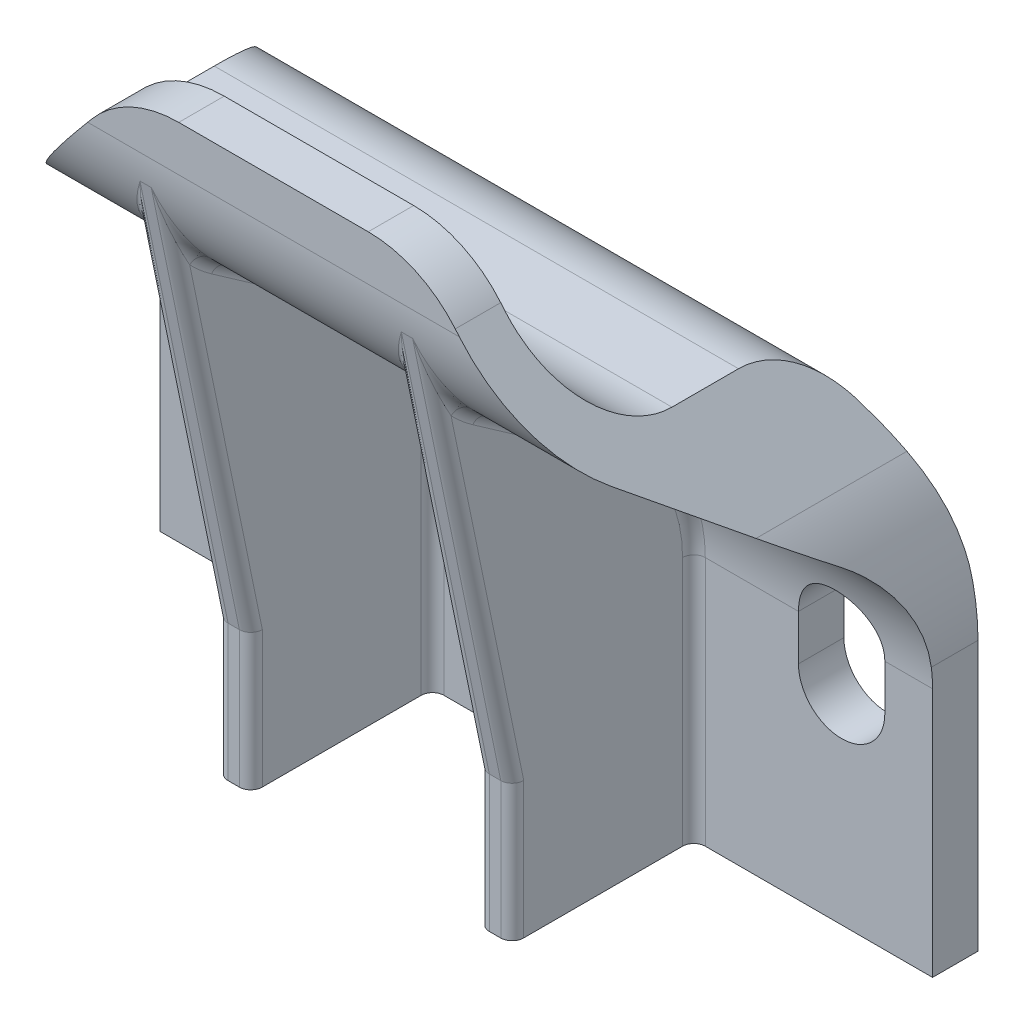
SolidWorks part; units mm, degrees
material "acero"
ref_plane "Alzado" through (0, 0, 0) normal (0, 0, 1) x (1, 0, 0)
ref_plane "Planta" through (0, 0, 0) normal (0, 1, 0) x (1, 0, 0)
ref_plane "Vista lateral" through (0, 0, 0) normal (1, 0, 0) x (0, 0, -1)
sketch "Croquis1" plane through (0, 0, 0) normal (1, 0, 0) x (0, 0, -1)
  line L0 (0, 0) -> (0, 8)
  line L1 (-5.0718, 16) -> (-8, 16)
  line L2 (-12, 20) -> (-12, 22)
  line L3 (-2, 0) -> (-2, 5)
  line L4 (-12, 22) -> (-14, 22)
  line L5 (-2, 0) -> (0, 0)
  line L6 (-14, 22) -> (-14, 20)
  line L7 (-11.4415, 15.0851) -> (-4.8458, 10.4668)
  arc A0 (-1.6077, 14) -> (-5.0718, 16) centre (-5.0718, 12) ccw
  arc A1 (-14, 20) -> (-11.4415, 15.0851) centre (-8, 20) ccw
  arc A2 (-8, 16) -> (-12, 20) centre (-8, 20) cw
  arc A3 (0, 8) -> (-1.6077, 14) centre (-12, 8) ccw
  arc A4 (-4.8458, 10.4668) -> (-2, 5) centre (-8.6737, 5) cw
  dimension "D5" = 12
  dimension "D7" = 2
  dimension "D13" = 22
  dimension "D14" = 12
  dimension "D3" = 35
  dimension "D6" = 16
  dimension "D8" = 4
  dimension "D2" = 8
  dimension "D4" = 2
  dimension "D10" = 5
extrude "Saliente-Extruir1" add sketch "Croquis1" along normal blind 34
sketch "Croquis2" plane through (0, 0, 2) normal (0, 0, 1) x (1, 0, 0)
  line L0 (17, 5) -> (17, 0) construction
  line L1 (4, 5) -> (4, 3) construction
  line L2 (5.9, 5) -> (5.9, 3)
  line L3 (34, 0) -> (0, 0) construction
  line L4 (2.1, 5) -> (2.1, 3)
  line L5 (34, 5) -> (0, 5) construction
  line L6 (30, 5) -> (30, 3) construction
  line L7 (28.1, 5) -> (28.1, 3)
  line L8 (31.9, 5) -> (31.9, 3)
  circle A0 centre (4, 3) radius 1.9 construction
  circle A1 centre (30, 3) radius 1.9 construction
  circle A2 centre (4, 3) radius 1.5 construction
  circle A3 centre (30, 3) radius 1.5 construction
  circle A4 centre (4, 3) radius 3.25 construction
  arc A5 (5.9, 5) -> (2.1, 5) centre (4, 5) ccw
  arc A6 (2.1, 3) -> (5.9, 3) centre (4, 3) ccw
  arc A7 (28.1, 5) -> (31.9, 5) centre (30, 5) cw
  arc A8 (31.9, 3) -> (28.1, 3) centre (30, 3) cw
  point P7 (4, 4)
  point P20 (30, 4)
  dimension "D1" = 26
  dimension "D2" = 6.5
  dimension "D3" = 3
  dimension "D4" = 3.8
  dimension "D5" = 3
  dimension "D6" = 2
extrude "Cortar-Extruir1" cut sketch "Croquis2" against normal through all both and the other way through all
chamfer "Chaflán2" [suppressed] distance 0.4 angle 60
ref_plane "Plano1" through (17, 0, 0) normal (-1, 0, 0) x (0, 0, 1)
sketch "Croquis3" plane through (17, 0, 0) normal (-1, 0, 0) x (0, 0, 1)
  line L0 (2, 0) -> (10, 0)
  line L1 (10, 0) -> (13.8762, 18.7876)
  line L2 (2, 0) -> (2, 5)
  line L3 (4.8458, 10.4668) -> (11.4415, 15.0851)
  arc A0 (11.4415, 15.0851) -> (14, 20) centre (8, 20) ccw construction
  arc A1 (2, 5) -> (4.8458, 10.4668) centre (8.6737, 5) cw
  arc A2 (11.4415, 15.0851) -> (13.8762, 18.7876) centre (8, 20) ccw
  dimension "D1" = 8
extrude "Saliente-Extruir2" add sketch "Croquis3" along normal blind 1.5 from offset 5
extrude "Saliente-Extruir3" add sketch "Croquis3<2>" against normal blind 1.5 from offset 5 offset against normal yes
sketch "Croquis3<2>" plane through (17, 0, 0) normal (-1, 0, 0) x (0, 0, 1) same geometry as "Croquis3"
sketch "Croquis4" plane through (0, 0, 0) normal (0, 0, -1) x (-1, 0, 0)
  line L0 (-10.5, 18.7876) -> (-10.5, 22) construction
  line L1 (-34, 22) -> (0, 22) construction
  line L2 (-17, 0) -> (-17, 22) construction
  line L3 (-22, 0) -> (-12, 0) construction
  line L4 (-34, 22) -> (-34, 9.4866)
  line L5 (0, 9.4866) -> (-10.5, 22)
  line L6 (-10.5, 22) -> (0, 22)
  line L7 (0, 22) -> (0, 9.4866)
  line L8 (-23.5, 22) -> (-34, 22)
  line L9 (-34, 9.4866) -> (-23.5, 22)
  dimension "D1" = 50
extrude "Cortar-Extruir2" cut sketch "Croquis4" against normal through all
fillet "Redondeo7" radius 5 2 edges at (23.5, 22, 13) (10.5, 22, 13)
fillet "Redondeo8" radius 10 2 edges at (34, 9.4866, 1.9128) (0, 9.4866, 1.9128)
fillet "Redondeo9" radius 0.5 20 edges at (22, 16.7033, 13.0132) (22, 12.7759, 8.1436) (22, 2.5, 2) (23.5, 16.7033, 13.0132) (23.5, 12.7759, 8.1436) (23.5, 2.5, 2) (12, 16.7033, 13.0132) (12, 12.7759, 8.1436) (12, 2.5, 2) (10.5, 16.7033, 13.0132) (10.5, 12.7759, 8.1436) (10.5, 8.0816, 2.7541) (22, 8.0816, 2.7541) (23.5, 8.0816, 2.7541) (12, 8.0816, 2.7541) (10.5, 2.5, 2) (10.5, 9.3938, 11.9381) (12, 9.3938, 11.9381) (22, 9.3938, 11.9381) (23.5, 9.3938, 11.9381)
sketch "Croquis5" plane through (0, 0, 0) normal (0, -1, 0) x (1, 0, 0)
  line L12 (0, 2) -> (0, 0)
  line L13 (0, 0) -> (34, 0)
  line L14 (34, 0) -> (34, 2)
  line L15 (34, 2) -> (24, 2)
  line L16 (23.5, 2.5) -> (23.5, 9.4895)
  line L17 (23, 10) -> (22.5, 10)
  line L18 (22, 9.4895) -> (22, 2.5)
  line L19 (21.5, 2) -> (12.5, 2)
  line L20 (12, 2.5) -> (12, 9.4895)
  line L21 (11.5, 10) -> (11, 10)
  line L22 (10.5, 9.4895) -> (10.5, 2.5)
  line L23 (10, 2) -> (0, 2)
  line L24 (0, 2) -> (0, 0)
  line L25 (0, 0) -> (34, 0)
  line L26 (34, 0) -> (34, 2)
  line L27 (34, 2) -> (24, 2)
  line L28 (23.5, 2.5) -> (23.5, 9.4895)
  line L29 (23, 10) -> (22.5, 10)
  line L30 (22, 9.4895) -> (22, 2.5)
  line L31 (21.5, 2) -> (12.5, 2)
  line L32 (12, 2.5) -> (12, 9.4895)
  line L33 (11.5, 10) -> (11, 10)
  line L34 (10.5, 9.4895) -> (10.5, 2.5)
  line L35 (10, 2) -> (0, 2)
  arc A11 (23.5, 2.5) -> (24, 2) centre (24, 2.5) ccw
  arc A12 (21.5, 2) -> (22, 2.5) centre (21.5, 2.5) ccw
  arc A13 (12, 2.5) -> (12.5, 2) centre (12.5, 2.5) ccw
  arc A14 (10, 2) -> (10.5, 2.5) centre (10, 2.5) ccw
  arc A19 (23.5, 2.5) -> (24, 2) centre (24, 2.5) ccw
  arc A20 (21.5, 2) -> (22, 2.5) centre (21.5, 2.5) ccw
  arc A21 (12, 2.5) -> (12.5, 2) centre (12.5, 2.5) ccw
  arc A22 (10, 2) -> (10.5, 2.5) centre (10, 2.5) ccw
  ellipse E4 centre (23, 9.4895) end of major axis (23, 10) minor radius 0.5 (23.5, 9.4895) -> (23, 10) ccw
  ellipse E5 centre (22.5, 9.4895) end of major axis (22.5, 8.9789) minor radius 0.5 (22.5, 10) -> (22, 9.4895) ccw
  ellipse E6 centre (11.5, 9.4895) end of major axis (11.5, 8.9789) minor radius 0.5 (12, 9.4895) -> (11.5, 10) ccw
  ellipse E7 centre (11, 9.4895) end of major axis (11, 10) minor radius 0.5 (11, 10) -> (10.5, 9.4895) ccw
  ellipse E8 centre (23, 9.4895) end of major axis (23, 10) minor radius 0.5 (23.5, 9.4895) -> (23, 10) ccw
  ellipse E9 centre (22.5, 9.4895) end of major axis (22.5, 8.9789) minor radius 0.5 (22.5, 10) -> (22, 9.4895) ccw
  ellipse E10 centre (11.5, 9.4895) end of major axis (11.5, 8.9789) minor radius 0.5 (12, 9.4895) -> (11.5, 10) ccw
  ellipse E11 centre (11, 9.4895) end of major axis (11, 10) minor radius 0.5 (11, 10) -> (10.5, 9.4895) ccw
  dimension "D1" = 0
extrude "Saliente-Extruir4" add sketch "Croquis5" along normal blind 6
